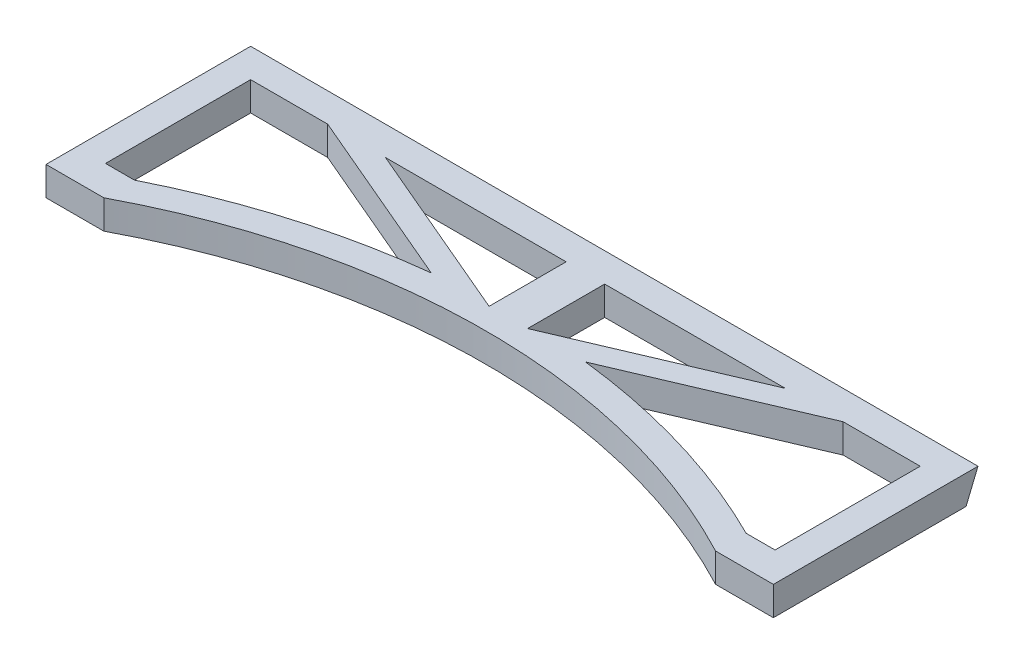
SolidWorks part; units mm, degrees
ref_plane "Front Plane" through (0, 0, 0) normal (0, 0, 1) x (1, 0, 0)
ref_plane "Top Plane" through (0, 0, 0) normal (0, 1, 0) x (1, 0, 0)
ref_plane "Right Plane" through (0, 0, 0) normal (1, 0, 0) x (0, 0, -1)
sketch "Sketch1" plane through (0, 0, 0) normal (0, 1, 0) x (1, 0, 0)
  line L0 (-119.8562, 0) -> (119.8562, 0)
  line L1 (-119.8562, 0) -> (-119.8562, -67.4348)
  line L2 (119.8562, 0) -> (119.8563, -67.4348)
  line L3 (-119.8562, -67.4348) -> (-100.8062, -67.4348)
  line L4 (119.8563, -67.4348) -> (100.8063, -67.4348)
  line L5 (-119.8562, -67.4348) -> (-100.8062, -67.4348) construction
  arc A1 (-100.8062, -67.4348) -> (100.8063, -67.4348) centre (0, -258.3561) cw
  point P2 (0, 0)
  dimension "D3" = 215.9
  dimension "D1" = 239.7125
  dimension "D4" = 19.05
  dimension "D5" = 19.05
extrude "Boss-Extrude1" add sketch "Sketch1" along normal blind 9.525
chamfer "Chamfer1" distance 3.9348 distance2 9.525 1 edges at (0, 0, 0) first distance on face at (0, 0, 40.7934)
sketch "Sketch3" plane through (0, 9.525, 0) normal (0, 1, 0) x (1, 0, 0)
  line L0 (-110.3312, -57.3469) -> (-110.3312, -9.525)
  line L1 (-110.3312, -9.525) -> (-84.9312, -9.525)
  line L3 (-119.8562, 0) -> (-119.8562, -67.4348) construction
  line L4 (119.8562, 0) -> (-119.8562, 0) construction
  line L5 (-84.9312, -9.525) -> (-25.4, -34.925)
  line L7 (-65.8812, -9.525) -> (-6.35, -34.925)
  line L8 (-6.35, -34.925) -> (-6.35, -9.525)
  line L9 (-6.35, -9.525) -> (-65.8812, -9.525)
  line L10 (0, 0) -> (0, -42.4561) construction
  line L17 (-110.3312, -57.3469) -> (-100.8062, -57.3469)
  line L18 (110.3313, -57.3469) -> (100.8063, -57.3469)
  line L19 (6.35, -9.525) -> (65.8812, -9.525)
  line L20 (6.35, -34.925) -> (6.35, -9.525)
  line L21 (65.8812, -9.525) -> (6.35, -34.925)
  line L22 (84.9312, -9.525) -> (25.4, -34.925)
  line L23 (110.3312, -9.525) -> (84.9312, -9.525)
  line L24 (110.3313, -57.3469) -> (110.3312, -9.525)
  arc A7 (-100.8062, -57.3469) -> (-25.4, -34.925) centre (0, -258.3561) cw
  arc A8 (100.8063, -67.4348) -> (-100.8062, -67.4348) centre (0, -258.3561) ccw construction
  arc A9 (100.8063, -57.3469) -> (25.4, -34.925) centre (0, -258.3561) ccw
  point P2 (0, -44.1568)
  point P7 (0, -55.5027)
  point P24 (-25.699, -47.625)
  point P30 (-96.6543, -67.983)
  point P31 (-102.3591, -70.793)
  point P32 (0, 0)
  point P34 (-82.9311, -9.525)
  dimension "D1" = 9.525
  dimension "D3" = 12.7
  dimension "D6" = 25.4
  dimension "D2" = 9.525
  dimension "D4" = 19.05
  dimension "D5" = 25.4
extrude "Cut-Extrude1" cut sketch "Sketch3" against normal through all
